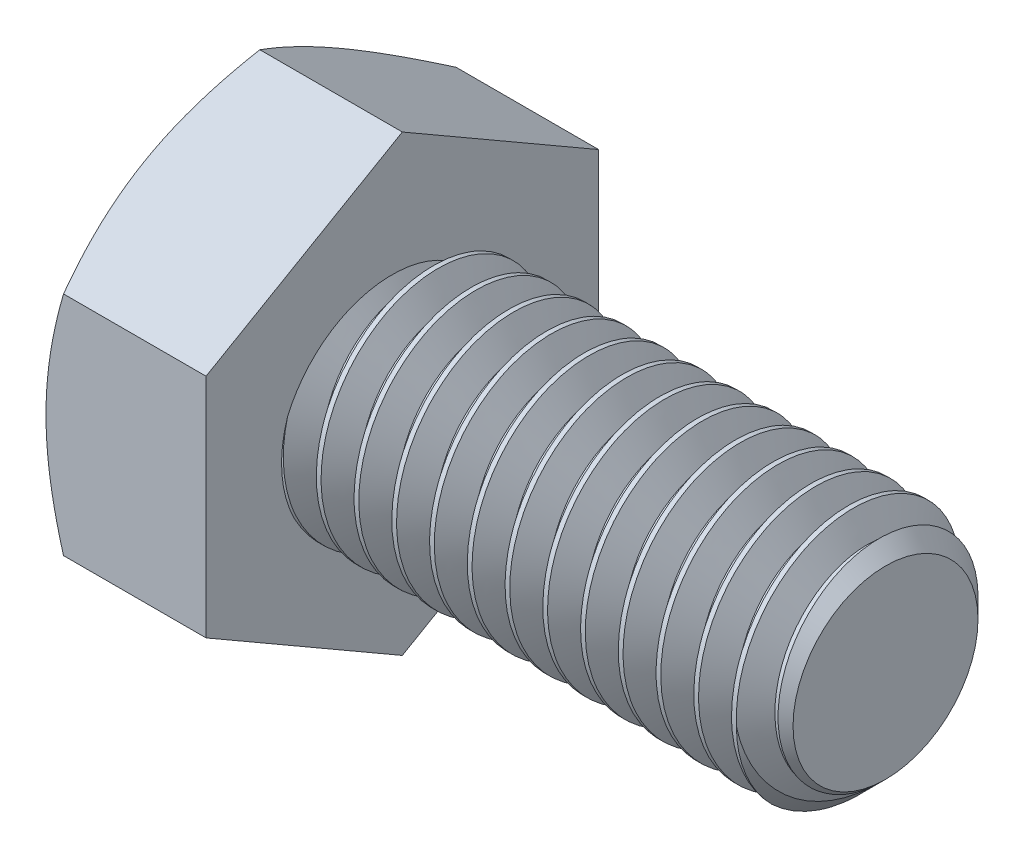
SolidWorks part; units mm, degrees
ref_plane "Front Plane" through (0, 0, 0) normal (0, 0, 1) x (1, 0, 0)
ref_plane "Top Plane" through (0, 0, 0) normal (0, 1, 0) x (1, 0, 0)
ref_plane "Right Plane" through (0, 0, 0) normal (1, 0, 0) x (0, 0, -1)
sketch "Sketch1" plane through (0, 0, 0) normal (0, 0, 1) x (1, 0, 0)
  line L0 (-10.65, 0) -> (10.65, 0) construction
  line L1 (-5.35, 6.5) -> (-5.35, -6.5) construction
  line L2 (-10.65, 6.5) -> (-10.65, -6.5) construction
  line L3 (10.65, 4) -> (10.65, -4) construction
  point P8 (6.275, -4)
  dimension "Thread Dia" = 8
  dimension "Hex" = 13
  dimension "Head Ht" = 5.3
  dimension "Length" = 16
  dimension "D1" = 4.375
ref_plane "Plane2" through (10.65, 0, 0) normal (1, 0, 0) x (0, 0, -1)
sketch "Sketch2" plane through (10.65, 0, 0) normal (1, 0, 0) x (0, 0, -1)
  circle A0 centre (0, 0) radius 4
extrude "Boss-Extrude1" add sketch "Sketch2" against normal up to vertex (16 mm away) up to point (-5.35, -6.5, 0)
sketch "Sketch4" plane through (10.65, 0, 0) normal (1, 0, 0) x (0, 0, -1)
  circle A1 centre (0, 0) radius 4
  circle A2 centre (0, 0) radius 4
  dimension "D1" = 0
curve "Helix/Spiral1" pitch 1.25 height 17.25 turns 13.8 parameters "Pitch"=1.25
chamfer "Chamfer1" distance 0.9375 angle 45 1 edges at (10.65, 0, -4)
sketch "Sketch5" plane through (0, 0, 0) normal (0, 0, 1) x (1, 0, 0)
  line L0 (10.65, 4) -> (11.1187, 3.1881)
  line L1 (11.1187, 3.1881) -> (11.275, 3.1881)
  line L2 (11.275, 3.1881) -> (11.7437, 4)
  line L3 (10.65, 4) -> (11.7437, 4)
  line L4 (11.1969, 3.1881) -> (11.1969, 4) construction
  line L5 (10.8844, 3.5941) -> (11.5094, 3.5941) construction
  line L6 (10.65, -4) -> (10.65, 4) construction
  dimension "D1" = 60
  dimension "D2" = 0.1562
  dimension "D3" = 0.625
sweep "Cut-Sweep1" cut profiles "Sketch5" path "Helix/Spiral1" align with end faces yes
sketch "Sketch3" plane through (-5.35, 0, 0) normal (-1, 0, 0) x (0, 0, 1)
  line L0 (0, 6.5) -> (0, -6.5) construction
  line L1 (-6.5, -3.7528) -> (0, -7.5056)
  line L2 (0, -7.5056) -> (6.5, -3.7528)
  line L3 (6.5, -3.7528) -> (6.5, 3.7528)
  line L4 (6.5, 3.7528) -> (0, 7.5056)
  line L5 (0, 7.5056) -> (-6.5, 3.7528)
  line L6 (-6.5, 3.7528) -> (-6.5, -3.7528)
  circle A0 centre (0, 0) radius 6.5 construction
extrude "Boss-Extrude2" add sketch "Sketch3" along normal up to vertex (5.3 mm away) up to point (-10.65, -6.5, 0)
sketch "Sketch6" plane through (-10.65, 0, 0) normal (-1, 0, 0) x (0, 0, 1)
  circle A0 centre (0, 0) radius 6.5 construction
  circle A1 centre (0, 0) radius 6.5
extrude "Cut-Extrude1" cut sketch "Sketch6" against normal through all draft 60 flip side to cut
sketch "Sketch9" plane through (0, 0, 0) normal (0, 0, 1) x (1, 0, 0)
  line L0 (-5.35, 4) -> (-5.35, 0)
  line L1 (-5.35, 0) -> (-3.35, 0)
  line L2 (-3.35, 0) -> (-7.35, 4)
  line L3 (-7.35, 4) -> (-5.35, 4)
  line L4 (-10.65, 0) -> (10.65, 0) construction
  line L5 (-5.35, 6.5) -> (-5.35, -6.5) construction
  line L6 (10.65, 4) -> (10.65, -4) construction
  dimension "D1" = 45
  dimension "MinThreadLg" = 18
revolve "Revolve1" [suppressed] add sketch "Sketch9" angle 360 about L1
equation "\"D2@Sketch5\" = \"Pitch@Helix/Spiral1\"*.125"
equation "\"D3@Sketch5\" = \"Pitch@Helix/Spiral1\"*.50"
equation "\"D3@Helix/Spiral1\" = \"Length@Sketch1\"+\"Pitch@Helix/Spiral1\""
equation "\"D1@Chamfer1\" = \"Pitch@Helix/Spiral1\"*.750"
equation "\"D1@Sketch1\" = \"Pitch@Helix/Spiral1\"*3.50"
